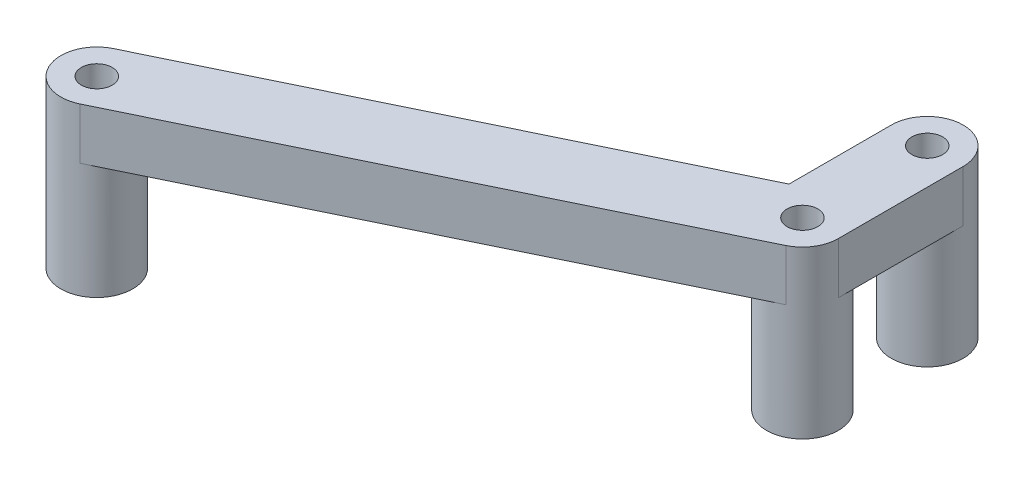
SolidWorks part; units mm, degrees
ref_plane "Front Plane" through (0, 0, 0) normal (0, 0, 1) x (1, 0, 0)
ref_plane "Top Plane" through (0, 0, 0) normal (0, 1, 0) x (1, 0, 0)
ref_plane "Right Plane" through (0, 0, 0) normal (1, 0, 0) x (0, 0, -1)
other "Bounding Box"
ref_plane "Default Plane" through (13.8565, 3.175, 6.7999) normal (0, -1, 0) x (-1, 0, 0)
sketch "Sketch1" plane through (0, 0, 0) normal (0, 1, 0) x (1, 0, 0)
  line L0 (-17.1831, -10.5283) -> (-15.4051, -10.5283) construction
  line L1 (-17.1831, -13.2588) -> (17.1831, -13.2588) construction
  line L2 (-17.1831, -13.2588) -> (-17.1831, 13.2588) construction
  line L3 (-17.1831, 13.2588) -> (17.1831, 13.2588) construction
  line L4 (17.1831, -13.2588) -> (17.1831, 13.2588) construction
  line L5 (-17.1831, -13.2588) -> (17.1831, 13.2588) construction
  line L6 (-17.1831, 13.2588) -> (17.1831, -13.2588) construction
  line L7 (-14.4526, -11.4808) -> (-14.4526, -13.2588) construction
  line L8 (14.9606, 12.3952) -> (14.9606, 13.2588) construction
  line L10 (15.9131, 11.4427) -> (17.1831, 11.4427) construction
  line L12 (17.1831, 11.4427) -> (17.1831, 3.7211)
  line L13 (12.7381, 11.4427) -> (12.7381, 5.114)
  line L14 (-13.4836, -12.5284) -> (15.9296, 1.721)
  line L15 (-15.4216, -8.5282) -> (12.7381, 5.114)
  line L16 (14.9606, 10.4902) -> (14.9606, 4.6736) construction
  circle A0 centre (-14.4526, -10.5283) radius 0.9525
  circle A1 centre (14.9606, 11.4427) radius 0.9525
  arc A2 (17.1831, 11.4427) -> (12.7381, 11.4427) centre (14.9606, 11.4427) ccw
  arc A3 (-15.4216, -8.5282) -> (-13.4836, -12.5284) centre (-14.4526, -10.5283) ccw
  circle A4 centre (14.9606, 3.7211) radius 0.9525
  arc A5 (15.9296, 1.721) -> (17.1831, 3.7211) centre (14.9606, 3.7211) ccw
  point P0 (0, 0)
  dimension "D1" = 1.905
  dimension "D7" = 1.27
  dimension "D2" = 26.5176
  dimension "D3" = 34.3662
  dimension "D4" = 1.778
  dimension "D5" = 1.27
  dimension "D6" = 0.8636
  dimension "D8" = 5.8166
extrude "Boss-Extrude1" add sketch "Sketch1" along normal blind 3.175
sketch "Sketch2" plane through (0, 0, 0) normal (0, -1, 0) x (1, 0, 0)
  circle A0 centre (-14.4526, 10.5283) radius 0.9525
  circle A1 centre (14.9606, -3.7211) radius 0.9525
  circle A2 centre (14.9606, -11.4427) radius 0.9525
  circle A3 centre (14.9606, -11.4427) radius 2.2225
  circle A4 centre (14.9606, -3.7211) radius 2.2225
  circle A5 centre (-14.4526, 10.5283) radius 2.2225
  circle A6 centre (-14.4526, 10.5283) radius 0.9525 construction
  arc A7 (-13.4836, 12.5284) -> (-15.4216, 8.5282) centre (-14.4526, 10.5283) ccw construction
extrude "Boss-Extrude2" add sketch "Sketch2" along normal blind 10.287 from surface starting at face at (14.9606, 3.175, -10.4902)
